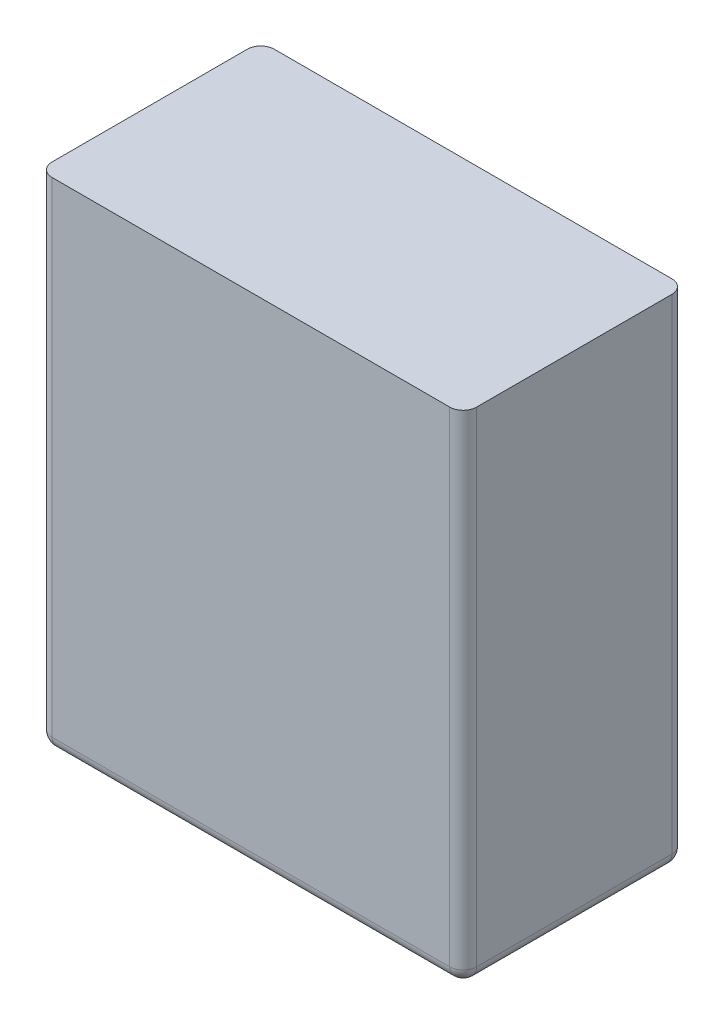
SolidWorks part; units mm, degrees
ref_plane "Alzado" through (0, 0, 0) normal (0, 0, 1) x (1, 0, 0)
ref_plane "Planta" through (0, 0, 0) normal (0, 1, 0) x (1, 0, 0)
ref_plane "Vista lateral" through (0, 0, 0) normal (1, 0, 0) x (0, 0, -1)
sketch "Croquis1" plane through (0, 0, 0) normal (0, 0, 1) x (1, 0, 0)
  line L1 (-15.765, 37) -> (15.765, 37)
  line L2 (-15.765, 37) -> (-15.765, -37)
  line L3 (-15.765, -37) -> (15.765, -37)
  line L4 (15.765, 37) -> (15.765, -37)
  line L5 (-15.765, 37) -> (15.765, -37) construction
  line L6 (-15.765, -37) -> (15.765, 37) construction
  point P0 (0, 0)
  dimension "D1" = 31.53
  dimension "D2" = 74
extrude "Saliente-Extruir1" add sketch "Croquis1" along normal blind 16.5
fillet "Redondeo2" radius 1 12 edges at (-15.765, -37, 8.25) (0, -37, 0) (0, 37, 0) (-15.765, 0, 0) (15.765, 0, 0) (15.765, -37, 8.25) (0, -37, 16.5) (-15.765, 0, 16.5) (15.765, 0, 16.5) (15.765, 37, 8.25) (0, 37, 16.5) (-15.765, 37, 8.25)
sketch "Croquis2" plane through (0, 0, 16.5) normal (0, 0, 1) x (1, 0, 0)
  line L1 (-15.8476, 37.2158) -> (15.765, 37.2158)
  line L2 (-15.8476, 37.2158) -> (-15.8476, 0)
  line L3 (-15.8476, 0) -> (15.765, 0)
  line L4 (15.765, 37.2158) -> (15.765, 0)
  line L5 (15.765, 36) -> (15.765, -36) construction
  point P4 (-15.8476, 37.2158)
  point P7 (15.765, 0)
  point P9 (0, 0)
  point P11 (0, 0)
extrude "Cortar-Extruir1" cut sketch "Croquis2" against normal through all
sketch "Croquis3" plane through (0, 0, 0) normal (0, 0, 1) x (1, 0, 0)
  line L0 (-14.765, 0) -> (-15.765, 0) construction
  line L1 (15.765, -37) -> (-15.765, -37)
  line L2 (15.765, -37) -> (15.765, 0)
  line L3 (15.765, 0) -> (-15.765, 0)
  line L4 (-15.765, -37) -> (-15.765, 0)
  line L5 (15.765, -37) -> (-15.765, 0) construction
  line L6 (15.765, 0) -> (-15.765, -37) construction
  line L7 (-15.765, -36) -> (-15.765, 0) construction
  point P0 (0, -18.5)
  point P9 (16.0045, -38.012)
  point P11 (-15.765, -37.4002)
  dimension "D1" = 37
  dimension "D2" = 31.53
sketch "Croquis4" plane through (0, 0, 0) normal (1, 0, 0) x (0, 0, -1)
  line L0 (0, 0) -> (0, -37) construction
  line L1 (0, -37) -> (-16.5, -37)
  line L2 (0, -37) -> (0, 0)
  line L3 (0, 0) -> (-16.5, 0)
  line L4 (-16.5, -37) -> (-16.5, 0)
  line L5 (0, -37) -> (-16.5, 0) construction
  line L6 (0, 0) -> (-16.5, -37) construction
  line L7 (0, -37) -> (0, 0) construction
  point P0 (-8.25, -18.5)
  point P6 (0, 0)
  point P8 (0, -37)
  point P13 (-16.5, -37)
  dimension "D1" = 16.5
